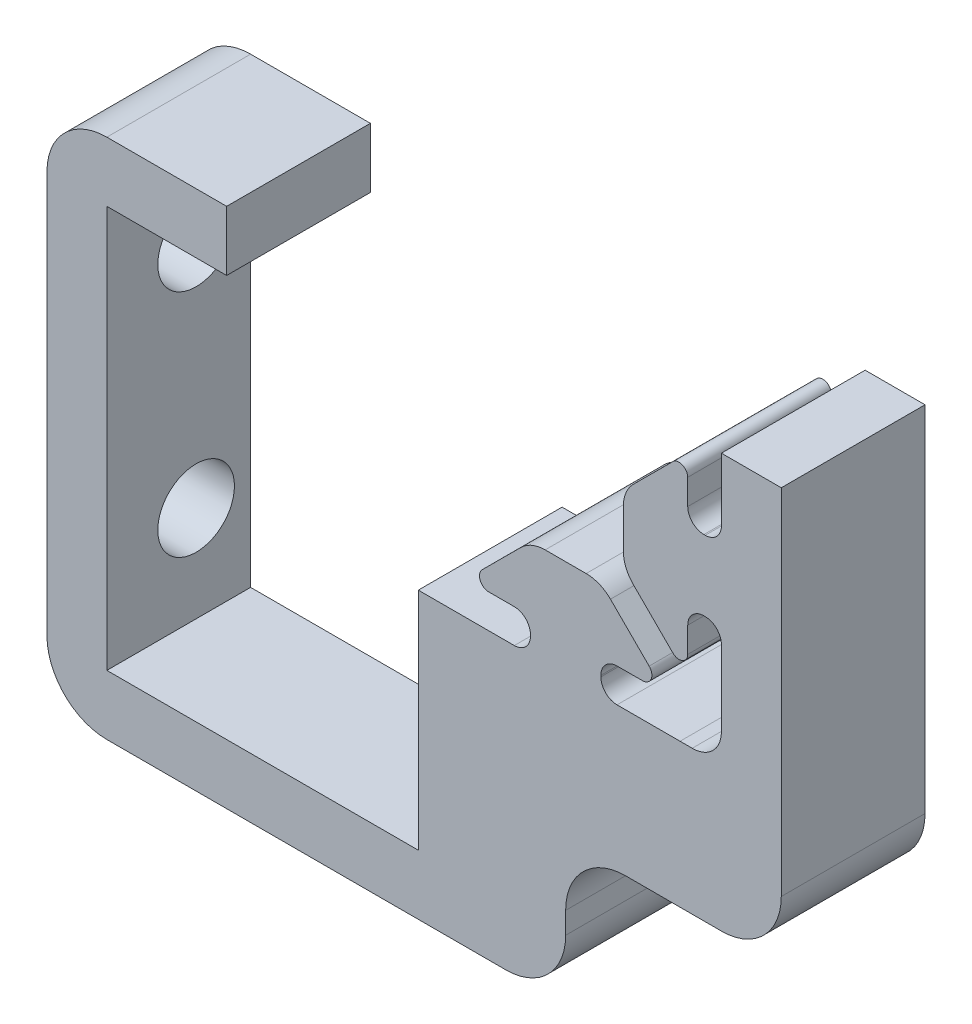
SolidWorks part; units mm, degrees
ref_plane "Front Plane" through (0, 0, 0) normal (0, 0, 1) x (1, 0, 0)
ref_plane "Top Plane" through (0, 0, 0) normal (0, 1, 0) x (1, 0, 0)
ref_plane "Right Plane" through (0, 0, 0) normal (1, 0, 0) x (0, 0, -1)
sketch "Sketch2" plane through (0, 0, 0) normal (0, 0, 1) x (1, 0, 0)
  line L0 (-12.7, 5.3171) -> (-12.7, 6.3331) construction
  line L1 (-37.9, 1.3473) -> (-12.7, 1.3473) construction
  line L2 (-37.9, 1.3473) -> (-37.9, -31.4027) construction
  line L3 (-37.9, -31.4027) -> (-12.7, -31.4027) construction
  line L4 (-12.7, 1.3473) -> (-12.7, -31.4027) construction
  line L5 (-37.9, 1.3473) -> (-12.7, -31.4027) construction
  line L6 (-37.9, -31.4027) -> (-12.7, 1.3473) construction
  line L7 (-12.7, 9.5504) -> (-12.6998, 10.5664) construction
  line L8 (-10.5664, 12.6998) -> (-9.5504, 12.7) construction
  line L9 (-6.3331, 12.7) -> (-5.3171, 12.7) construction
  line L10 (5.3171, 12.7) -> (6.3331, 12.7) construction
  line L11 (9.5504, 12.7) -> (10.5664, 12.6998) construction
  line L12 (12.6998, 10.5664) -> (12.7, 9.5504) construction
  line L13 (12.7, 6.3331) -> (12.7, 5.3171) construction
  line L14 (12.7, -5.3171) -> (12.7, -6.3331) construction
  line L15 (12.7, -9.5504) -> (12.6998, -10.5664) construction
  line L16 (10.5664, -12.6998) -> (9.5504, -12.7) construction
  line L17 (-10.5918, -13) -> (-5.3171, -13)
  line L18 (-5.3171, -13) -> (-4.2875, -13)
  line L19 (-2.9385, -11.651) -> (-2.9385, -11.5392)
  line L20 (-4.2875, -10.1902) -> (-6.4164, -10.1902)
  line L21 (-6.9677, -8.8575) -> (-3.7403, -5.636)
  line L22 (-1.7093, -4.7958) -> (1.7093, -4.7958)
  line L23 (3.7403, -5.636) -> (6.9677, -8.8575)
  line L24 (6.4164, -10.1902) -> (4.2875, -10.1902)
  line L25 (2.9385, -11.5392) -> (2.9385, -11.651)
  line L26 (4.2875, -13) -> (5.3171, -13)
  line L27 (5.3171, -13) -> (9.5505, -13)
  line L28 (10.5647, -12.9998) -> (9.5505, -13)
  line L29 (13, -9.5504) -> (12.9998, -10.5647)
  line L30 (13, -9.5504) -> (13, -6.3331)
  line L31 (13, -5.3171) -> (13, -6.3331)
  line L32 (13, -5.3171) -> (13, -4.2875)
  line L33 (11.651, -2.9385) -> (11.5392, -2.9385)
  line L34 (10.1902, -4.2875) -> (10.1902, -6.4021)
  line L35 (8.949, -6.917) -> (5.6529, -3.6284)
  line L36 (4.8085, -1.5932) -> (4.8085, 1.5932)
  line L37 (5.6529, 3.6284) -> (8.949, 6.917)
  line L38 (10.1902, 6.4021) -> (10.1902, 4.2875)
  line L39 (11.5392, 2.9385) -> (11.651, 2.9385)
  line L40 (13, 4.2875) -> (13, 5.3171)
  line L41 (13, 6.3331) -> (13, 5.3171)
  line L42 (13, 6.3331) -> (13, 9.5504)
  line L43 (13, 9.5504) -> (18, 9.5504)
  line L44 (18, 9.5504) -> (18, -25)
  line L45 (-12, -36.8027) -> (-43.3, -36.8027)
  line L46 (-43.3, -36.8027) -> (-43.3, -31.8027)
  line L47 (-38.3, -31.8027) -> (-12.3, -31.8027)
  line L48 (-12.3, -31.8027) -> (-12.3, -13)
  line L49 (-10.5918, -13) -> (-12.3, -13)
  line L50 (-43.3, -31.8027) -> (-43.3, 6.7473)
  line L51 (-43.3, 6.7473) -> (-28.3, 6.7473)
  line L52 (-28.3, 6.7473) -> (-28.3, 1.7473)
  line L53 (-28.3, 1.7473) -> (-38.3, 1.7473)
  line L54 (-38.3, 1.7473) -> (-38.3, -31.8027)
  line L55 (-12, -36.8027) -> (0, -36.8027)
  line L56 (0, -36.8027) -> (0, -25)
  line L57 (0, -25) -> (18, -25)
  line L88 (-7.1797, -8.6452) -> (-3.9523, -5.4237) construction
  line L89 (-1.7093, -4.4958) -> (1.7093, -4.4958) construction
  line L90 (3.9523, -5.4237) -> (7.1797, -8.6452) construction
  line L91 (6.4164, -10.4902) -> (4.2875, -10.4902) construction
  line L92 (3.2385, -11.5392) -> (3.2385, -11.651) construction
  line L93 (4.2875, -12.7) -> (5.3171, -12.7) construction
  line L94 (5.3171, -12.7) -> (9.5504, -12.7) construction
  line L95 (12.7, -9.5504) -> (12.7, -6.3331) construction
  line L96 (12.7, -5.3171) -> (12.7, -4.2875) construction
  line L97 (11.651, -3.2385) -> (11.5392, -3.2385) construction
  line L98 (10.4902, -4.2875) -> (10.4902, -6.4021) construction
  line L99 (8.7371, -7.1294) -> (5.441, -3.8408) construction
  line L100 (4.5085, -1.5932) -> (4.5085, 1.5932) construction
  line L101 (5.441, 3.8408) -> (8.7371, 7.1294) construction
  line L102 (10.4902, 6.4021) -> (10.4902, 4.2875) construction
  line L103 (11.5392, 3.2385) -> (11.651, 3.2385) construction
  line L104 (12.7, 4.2875) -> (12.7, 5.3171) construction
  line L105 (12.7, 6.3331) -> (12.7, 9.5504) construction
  line L106 (9.5504, 12.7) -> (6.3331, 12.7) construction
  line L107 (5.3171, 12.7) -> (4.2875, 12.7) construction
  line L108 (3.2385, 11.651) -> (3.2385, 11.5392) construction
  line L109 (4.2875, 10.4902) -> (6.4768, 10.4902) construction
  line L110 (7.207, 8.7244) -> (3.8983, 5.4232) construction
  line L111 (1.6558, 4.4958) -> (-1.6558, 4.4958) construction
  line L112 (-3.8983, 5.4232) -> (-7.207, 8.7244) construction
  line L113 (-6.4768, 10.4902) -> (-4.2875, 10.4902) construction
  line L114 (-3.2385, 11.5392) -> (-3.2385, 11.651) construction
  line L115 (-4.2875, 12.7) -> (-5.3171, 12.7) construction
  line L116 (-6.3331, 12.7) -> (-9.5504, 12.7) construction
  line L117 (-12.7, 9.5504) -> (-12.7, 6.3331) construction
  line L118 (-12.7, 5.3171) -> (-12.7, 4.2875) construction
  line L119 (-11.651, 3.2385) -> (-11.5392, 3.2385) construction
  line L120 (-10.4902, 4.2875) -> (-10.4902, 6.4021) construction
  line L121 (-8.7371, 7.1294) -> (-5.441, 3.8408) construction
  line L122 (-4.5085, 1.5932) -> (-4.5085, -1.5932) construction
  line L123 (-5.441, -3.8408) -> (-8.7371, -7.1294) construction
  line L124 (-10.4902, -6.4021) -> (-10.4902, -4.2875) construction
  line L125 (-11.5392, -3.2385) -> (-11.651, -3.2385) construction
  line L126 (-12.7, -4.2875) -> (-12.7, -5.3171) construction
  line L128 (-10.5918, -12.7) -> (-5.3171, -12.7) construction
  line L129 (-5.3171, -12.7) -> (-4.2875, -12.7) construction
  line L130 (-3.2385, -11.651) -> (-3.2385, -11.5392) construction
  line L131 (-4.2875, -10.4902) -> (-6.4164, -10.4902) construction
  line L132 (-13, -4.2875) -> (-13, -5.3171) construction
  line L133 (-10.1902, -6.4021) -> (-10.1902, -4.2875) construction
  line L134 (-11.5392, -2.9385) -> (-11.651, -2.9385) construction
  line L135 (-5.6529, -3.6284) -> (-8.949, -6.917) construction
  line L136 (-4.8085, 1.5932) -> (-4.8085, -1.5932) construction
  line L137 (-8.949, 6.917) -> (-5.6529, 3.6284) construction
  line L138 (-10.1902, 4.2875) -> (-10.1902, 6.4021) construction
  line L139 (-11.651, 2.9385) -> (-11.5392, 2.9385) construction
  line L140 (-13, 5.3171) -> (-13, 6.3331) construction
  line L141 (-13, 5.3171) -> (-13, 4.2875) construction
  line L142 (-13, 9.5504) -> (-13, 6.3331) construction
  line L143 (-13, 9.5504) -> (-12.9998, 10.5647) construction
  line L144 (-10.5647, 12.9998) -> (-9.5505, 13) construction
  line L145 (-6.3331, 13) -> (-9.5505, 13) construction
  line L146 (-6.3331, 13) -> (-5.3171, 13) construction
  line L147 (-4.2875, 13) -> (-5.3171, 13) construction
  line L148 (-2.9385, 11.5392) -> (-2.9385, 11.651) construction
  line L149 (-6.4768, 10.1902) -> (-4.2875, 10.1902) construction
  line L150 (-3.6864, 5.6355) -> (-6.9951, 8.9367) construction
  line L151 (1.6558, 4.7958) -> (-1.6558, 4.7958) construction
  line L152 (6.9951, 8.9367) -> (3.6864, 5.6355) construction
  line L153 (4.2875, 10.1902) -> (6.4768, 10.1902) construction
  line L154 (2.9385, 11.651) -> (2.9385, 11.5392) construction
  line L155 (5.3171, 13) -> (4.2875, 13) construction
  line L156 (5.3171, 13) -> (6.3331, 13) construction
  line L157 (9.5505, 13) -> (6.3331, 13) construction
  line L158 (9.5505, 13) -> (10.5647, 12.9998) construction
  line L159 (12.9998, 10.5647) -> (13, 9.5504) construction
  arc A0 (-4.2875, -13) -> (-2.9385, -11.651) centre (-4.2875, -11.651) ccw
  circle A1 centre (0, 0) radius 2.6035
  arc A2 (-2.9385, -11.5392) -> (-4.2875, -10.1902) centre (-4.2875, -11.5392) ccw
  arc A3 (-6.9677, -8.8575) -> (-6.4164, -10.1902) centre (-6.4164, -9.4098) ccw
  arc A4 (-1.7093, -4.7958) -> (-3.7403, -5.636) centre (-1.7093, -7.6708) ccw
  arc A5 (3.7403, -5.636) -> (1.7093, -4.7958) centre (1.7093, -7.6708) ccw
  arc A6 (6.4164, -10.1902) -> (6.9677, -8.8575) centre (6.4164, -9.4098) ccw
  arc A7 (4.2875, -10.1902) -> (2.9385, -11.5392) centre (4.2875, -11.5392) ccw
  arc A8 (2.9385, -11.651) -> (4.2875, -13) centre (4.2875, -11.651) ccw
  arc A9 (10.5647, -12.9998) -> (12.9998, -10.5647) centre (10.5918, -10.5918) ccw
  arc A10 (13, -4.2875) -> (11.651, -2.9385) centre (11.651, -4.2875) ccw
  arc A11 (11.5392, -2.9385) -> (10.1902, -4.2875) centre (11.5392, -4.2875) ccw
  arc A12 (8.949, -6.917) -> (10.1902, -6.4021) centre (9.4628, -6.4021) ccw
  arc A13 (4.8085, -1.5932) -> (5.6529, -3.6284) centre (7.6835, -1.5932) ccw
  arc A14 (5.6529, 3.6284) -> (4.8085, 1.5932) centre (7.6835, 1.5932) ccw
  arc A15 (10.1902, 6.4021) -> (8.949, 6.917) centre (9.4628, 6.4021) ccw
  arc A16 (10.1902, 4.2875) -> (11.5392, 2.9385) centre (11.5392, 4.2875) ccw
  arc A17 (11.651, 2.9385) -> (13, 4.2875) centre (11.651, 4.2875) ccw
  arc A18 (-10.5918, -12.7) -> (-10.5664, -12.6998) centre (-10.5918, -10.5918) ccw
  arc A104 (-7.1797, -8.6452) -> (-6.4164, -10.4902) centre (-6.4164, -9.4098) ccw construction
  arc A105 (-1.7093, -4.4958) -> (-3.9523, -5.4237) centre (-1.7093, -7.6708) ccw construction
  arc A106 (3.9523, -5.4237) -> (1.7093, -4.4958) centre (1.7093, -7.6708) ccw construction
  arc A107 (6.4164, -10.4902) -> (7.1797, -8.6452) centre (6.4164, -9.4098) ccw construction
  arc A108 (4.2875, -10.4902) -> (3.2385, -11.5392) centre (4.2875, -11.5392) ccw construction
  arc A109 (3.2385, -11.651) -> (4.2875, -12.7) centre (4.2875, -11.651) ccw construction
  arc A112 (10.5664, -12.6998) -> (12.6998, -10.5664) centre (10.5918, -10.5918) ccw construction
  arc A115 (12.7, -4.2875) -> (11.651, -3.2385) centre (11.651, -4.2875) ccw construction
  arc A116 (11.5392, -3.2385) -> (10.4902, -4.2875) centre (11.5392, -4.2875) ccw construction
  arc A117 (8.7371, -7.1294) -> (10.4902, -6.4021) centre (9.4628, -6.4021) ccw construction
  arc A118 (4.5085, -1.5932) -> (5.441, -3.8408) centre (7.6835, -1.5932) ccw construction
  arc A119 (5.441, 3.8408) -> (4.5085, 1.5932) centre (7.6835, 1.5932) ccw construction
  arc A120 (10.4902, 6.4021) -> (8.7371, 7.1294) centre (9.4628, 6.4021) ccw construction
  arc A121 (10.4902, 4.2875) -> (11.5392, 3.2385) centre (11.5392, 4.2875) ccw construction
  arc A122 (11.651, 3.2385) -> (12.7, 4.2875) centre (11.651, 4.2875) ccw construction
  arc A125 (12.6998, 10.5664) -> (10.5664, 12.6998) centre (10.5918, 10.5918) ccw construction
  arc A128 (4.2875, 12.7) -> (3.2385, 11.651) centre (4.2875, 11.651) ccw construction
  arc A129 (3.2385, 11.5392) -> (4.2875, 10.4902) centre (4.2875, 11.5392) ccw construction
  arc A130 (7.207, 8.7244) -> (6.4768, 10.4902) centre (6.4768, 9.4563) ccw construction
  arc A131 (1.6558, 4.4958) -> (3.8983, 5.4232) centre (1.6558, 7.6708) ccw construction
  arc A132 (-3.8983, 5.4232) -> (-1.6558, 4.4958) centre (-1.6558, 7.6708) ccw construction
  arc A133 (-6.4768, 10.4902) -> (-7.207, 8.7244) centre (-6.4768, 9.4563) ccw construction
  arc A134 (-4.2875, 10.4902) -> (-3.2385, 11.5392) centre (-4.2875, 11.5392) ccw construction
  arc A135 (-3.2385, 11.651) -> (-4.2875, 12.7) centre (-4.2875, 11.651) ccw construction
  arc A138 (-10.5664, 12.6998) -> (-12.6998, 10.5664) centre (-10.5918, 10.5918) ccw construction
  arc A141 (-12.7, 4.2875) -> (-11.651, 3.2385) centre (-11.651, 4.2875) ccw construction
  arc A142 (-11.5392, 3.2385) -> (-10.4902, 4.2875) centre (-11.5392, 4.2875) ccw construction
  arc A143 (-8.7371, 7.1294) -> (-10.4902, 6.4021) centre (-9.4628, 6.4021) ccw construction
  arc A144 (-4.5085, 1.5932) -> (-5.441, 3.8408) centre (-7.6835, 1.5932) ccw construction
  arc A145 (-5.441, -3.8408) -> (-4.5085, -1.5932) centre (-7.6835, -1.5932) ccw construction
  arc A146 (-10.4902, -6.4021) -> (-8.7371, -7.1294) centre (-9.4628, -6.4021) ccw construction
  arc A147 (-10.4902, -4.2875) -> (-11.5392, -3.2385) centre (-11.5392, -4.2875) ccw construction
  arc A148 (-11.651, -3.2385) -> (-12.7, -4.2875) centre (-11.651, -4.2875) ccw construction
  arc A151 (-12.6998, -10.5664) -> (-12.7, -10.5918) centre (-10.5918, -10.5918) ccw
  arc A154 (-4.2875, -12.7) -> (-3.2385, -11.651) centre (-4.2875, -11.651) ccw construction
  arc A155 (-3.2385, -11.5392) -> (-4.2875, -10.4902) centre (-4.2875, -11.5392) ccw construction
  arc A156 (-11.651, -2.9385) -> (-13, -4.2875) centre (-11.651, -4.2875) ccw construction
  arc A157 (-10.1902, -4.2875) -> (-11.5392, -2.9385) centre (-11.5392, -4.2875) ccw construction
  arc A158 (-10.1902, -6.4021) -> (-8.949, -6.917) centre (-9.4628, -6.4021) ccw construction
  arc A159 (-5.6529, -3.6284) -> (-4.8085, -1.5932) centre (-7.6835, -1.5932) ccw construction
  arc A160 (-4.8085, 1.5932) -> (-5.6529, 3.6284) centre (-7.6835, 1.5932) ccw construction
  arc A161 (-8.949, 6.917) -> (-10.1902, 6.4021) centre (-9.4628, 6.4021) ccw construction
  arc A162 (-11.5392, 2.9385) -> (-10.1902, 4.2875) centre (-11.5392, 4.2875) ccw construction
  arc A163 (-13, 4.2875) -> (-11.651, 2.9385) centre (-11.651, 4.2875) ccw construction
  arc A164 (-10.5647, 12.9998) -> (-12.9998, 10.5647) centre (-10.5918, 10.5918) ccw construction
  arc A165 (-2.9385, 11.651) -> (-4.2875, 13) centre (-4.2875, 11.651) ccw construction
  arc A166 (-4.2875, 10.1902) -> (-2.9385, 11.5392) centre (-4.2875, 11.5392) ccw construction
  arc A167 (-6.4768, 10.1902) -> (-6.9951, 8.9367) centre (-6.4768, 9.4563) ccw construction
  arc A168 (-3.6864, 5.6355) -> (-1.6558, 4.7958) centre (-1.6558, 7.6708) ccw construction
  arc A169 (1.6558, 4.7958) -> (3.6864, 5.6355) centre (1.6558, 7.6708) ccw construction
  arc A170 (6.9951, 8.9367) -> (6.4768, 10.1902) centre (6.4768, 9.4563) ccw construction
  arc A171 (2.9385, 11.5392) -> (4.2875, 10.1902) centre (4.2875, 11.5392) ccw construction
  arc A172 (4.2875, 13) -> (2.9385, 11.651) centre (4.2875, 11.651) ccw construction
  arc A173 (12.9998, 10.5647) -> (10.5647, 12.9998) centre (10.5918, 10.5918) ccw construction
  point P3 (-25.3, -15.0277)
  dimension "D13" = 12
  dimension "D1" = 32.75
  dimension "D2" = 25.2
  dimension "D3" = 11.3527
  dimension "D4" = 0.4
  dimension "D5" = 0.3
  dimension "D6" = 5
  dimension "D7" = 0.4
  dimension "D8" = 0.4
  dimension "D9" = 0.4
  dimension "D10" = 5
  dimension "D11" = 5
  dimension "D12" = 5
  dimension "D14" = 15
  dimension "D15" = 5
extrude "Boss-Extrude1" add sketch "Sketch2" along normal blind 12 contours L56 L57 L44 L43 L42 L41 L40 A17 L39 A16 L38 A15 L37 A14 L36 A13 L35 A12 L34 A11 L33 A10 L32 L31 L30 L29 A9 L28 L27 L26 A8 L25 A7 L24 A6 L23 A5 L22 A4 L21 A3 L20 A2 L19 A0 L18 L17 L49 L48 L47 L54 L53 L52 L51 L50 L46 L45 L55
fillet "Fillet1" radius 5 3 edges at (0, -25, 6) (0, -36.8027, 6) (18, -25, 6)
fillet "Fillet2" radius 5 2 edges at (-43.3, 6.7473, 6) (-43.3, -36.8027, 6)
sketch "Sketch3" plane through (-43.3, 0, 0) normal (-1, 0, 0) x (0, 0, 1)
  line L0 (7.45, -23.7927) -> (7.45, -26.9927) construction
  line L1 (0, -31.8027) -> (12, -31.8027) construction
  line L2 (7.45, -23.7927) -> (4.25, -23.7927) construction
  line L3 (0, -31.8027) -> (0, 1.7473) construction
  line L4 (7.45, -36.9446) -> (7.45, -7.7927) construction
  line L5 (7.45, -36.9446) -> (32.05, -36.9446) construction
  line L6 (7.45, -23.7927) -> (7.45, -20.5927) construction
  line L7 (10.65, -4.5927) -> (7.45, -4.5927) construction
  line L8 (7.45, -4.5927) -> (7.45, -7.7927) construction
  line L9 (7.45, -4.5927) -> (4.25, -4.5927) construction
  circle A0 centre (7.45, -23.7927) radius 3.2
  circle A2 centre (7.45, -4.5927) radius 3.2
  dimension "D1" = 6.4
  dimension "D4" = 12.8
  dimension "D5" = 6.4
  dimension "D2" = 4.81
  dimension "D3" = 4.25
  dimension "D6" = 4.25
extrude "Cut-Extrude1" cut sketch "Sketch3" against normal up to next
chamfer "Chamfer1" distance 0.2 angle 45 2 edges at (-43.3, -4.5927, 10.65) (-43.3, -23.7927, 10.65)
mirror "Mirror1" about plane through (11.651, 4.2875, 12) normal (0, 0, 1) of bodies 102
sketch "Sketch4" plane through (-43.3, 0, 0) normal (-1, 0, 0) x (0, 0, 1)
  line L0 (12, -31.8027) -> (12, -40.6808) construction
  line L2 (12, -40.6808) -> (-11.7294, -40.6808)
  line L3 (12, -40.6808) -> (12, 14.6189)
  line L4 (12, 14.6189) -> (-11.7294, 14.6189)
  line L5 (-11.7294, -40.6808) -> (-11.7294, 14.6189)
  dimension "D1" = 55.2997
  dimension "D2" = 23.7294
extrude "Cut-Extrude2" cut sketch "Sketch4" against normal through all both and the other way through all
